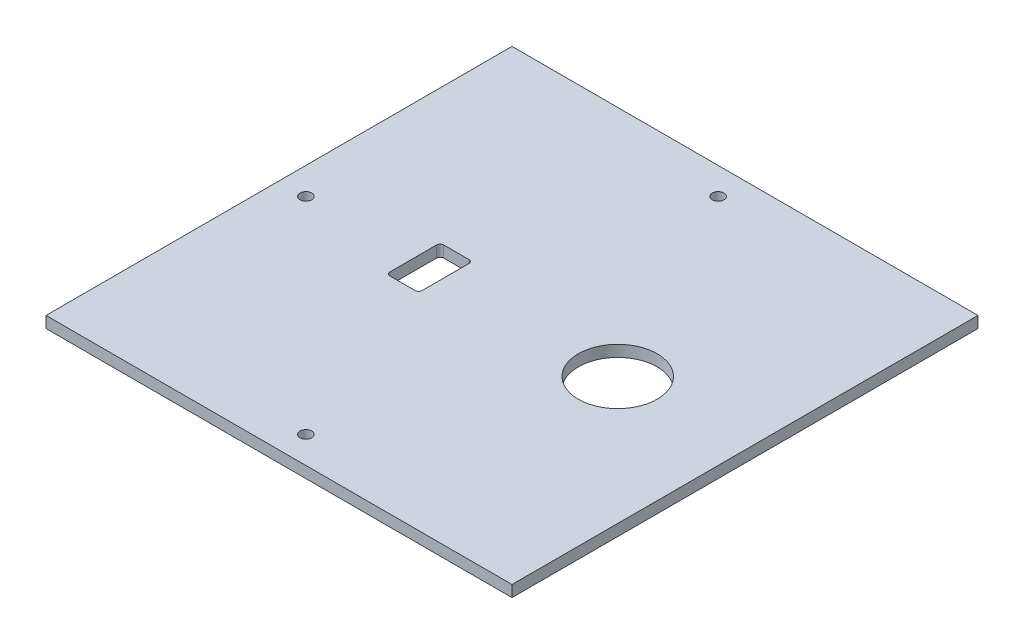
SolidWorks part; units mm, degrees
ref_plane "Front Plane" through (0, 0, 0) normal (0, 0, 1) x (1, 0, 0)
ref_plane "Top Plane" through (0, 0, 0) normal (0, 1, 0) x (1, 0, 0)
ref_plane "Right Plane" through (0, 0, 0) normal (1, 0, 0) x (0, 0, -1)
sketch "Sketch1" plane through (0, 0, 0) normal (0, 1, 0) x (1, 0, 0)
  line L1 (-60.5343, 66.954) -> (69.4657, 66.954)
  line L2 (-60.5343, 66.954) -> (-60.5343, -63.046)
  line L3 (-60.5343, -63.046) -> (69.4657, -63.046)
  line L4 (69.4657, 66.954) -> (69.4657, -63.046)
  line L5 (-60.5343, 66.954) -> (69.4657, -63.046) construction
  line L6 (-22.0803, 9.454) -> (-15.0803, 9.454)
  line L7 (-53.0343, 59.454) -> (61.9657, 59.454) construction
  line L8 (-53.0343, 59.454) -> (-53.0343, -55.546) construction
  line L9 (-53.0343, -55.546) -> (61.9657, -55.546) construction
  line L10 (61.9657, 59.454) -> (61.9657, -55.546) construction
  line L11 (-53.0343, 59.454) -> (61.9657, -55.546) construction
  line L12 (-23.0803, 8.454) -> (-23.0803, -4.546)
  line L29 (-22.0803, -5.546) -> (-15.0803, -5.546)
  line L30 (-14.0803, 8.454) -> (-14.0803, -4.546)
  line L31 (-23.0803, 9.454) -> (-14.0803, -5.546) construction
  line L32 (-23.0803, -5.546) -> (-14.0803, 9.454) construction
  circle A0 centre (-53.0343, 1.954) radius 1.65
  circle A1 centre (4.4657, 59.454) radius 1.65
  circle A3 centre (4.4657, -55.546) radius 1.65
  circle A13 centre (33.9657, 1.954) radius 11
  arc A22 (-23.0803, -4.546) -> (-22.0803, -5.546) centre (-22.0803, -4.546) ccw
  arc A23 (-15.0803, -5.546) -> (-14.0803, -4.546) centre (-15.0803, -4.546) ccw
  arc A24 (-15.0803, 9.454) -> (-14.0803, 8.454) centre (-15.0803, 8.454) cw
  arc A25 (-22.0803, 9.454) -> (-23.0803, 8.454) centre (-22.0803, 8.454) ccw
  point P0 (6.4197, 0)
  point P6 (4.4657, 1.954)
  point P21 (-18.5803, 1.954)
  point P37 (0, 0)
  point P38 (0, 0)
  dimension "D5" = 9
  dimension "D6" = 22
  dimension "D9" = 25
  dimension "D17" = 28
  dimension "D8" = 1
  dimension "D1" = 7.5
  dimension "D2" = 7.5
  dimension "D3" = 130
  dimension "D4" = 130
  dimension "D7" = 15
extrude "Boss-Extrude1" add sketch "Sketch1" along normal blind 3.175
